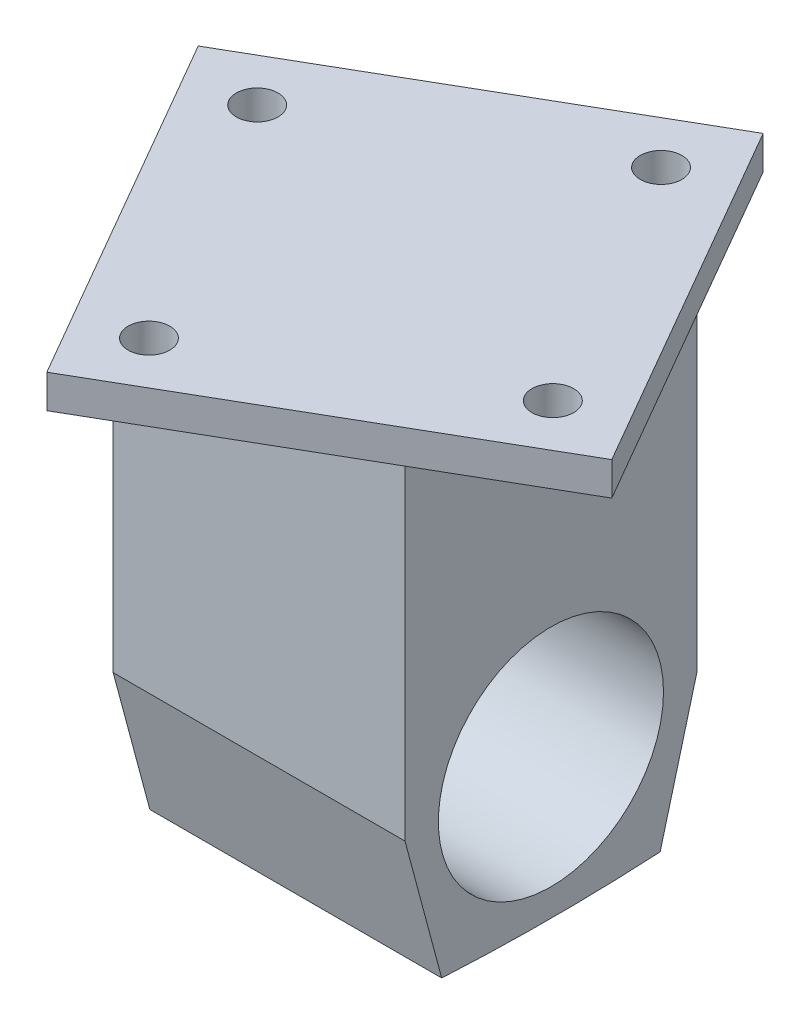
SolidWorks part; units mm, degrees
material "ABS"
ref_plane "Front Plane" through (0, 0, 0) normal (0, 0, 1) x (1, 0, 0)
ref_plane "Top Plane" through (0, 0, 0) normal (0, 1, 0) x (1, 0, 0)
ref_plane "Right Plane" through (0, 0, 0) normal (1, 0, 0) x (0, 0, -1)
sketch "Sketch1" plane through (0, 0, 0) normal (0, 1, 0) x (1, 0, 0)
  line L1 (-22.225, -22.225) -> (22.225, -22.225)
  line L2 (-22.225, -22.225) -> (-22.225, 22.225)
  line L3 (-22.225, 22.225) -> (22.225, 22.225)
  line L4 (22.225, -22.225) -> (22.225, 22.225)
  line L5 (-22.225, -22.225) -> (22.225, 22.225) construction
  line L6 (-22.225, 22.225) -> (22.225, -22.225) construction
  point P0 (0, 0)
extrude "Boss-Extrude1" add sketch "Sketch1" along normal blind 50.292
sketch "Sketch2" plane through (22.225, 0, 0) normal (1, 0, 0) x (0, 0, -1)
  line L0 (-22.225, 0) -> (-16.6371, -20.8543)
  line L1 (22.225, 0) -> (16.6371, -20.8543)
  line L2 (-22.225, 0) -> (22.225, 0)
  line L3 (-22.225, 0) -> (22.225, 0) construction
  arc A1 (16.6371, -20.8543) -> (-16.6371, -20.8543) centre (0, 278.6719) cw
  point P9 (0, 0)
  dimension "D1" = 21.59
  dimension "D2" = 21.59
  dimension "D3" = 75
  dimension "D4" = 75
extrude "Boss-Extrude2" add sketch "Sketch2" against normal up to vertex (44.45 mm away) contours L0 A1 L1 L2 up to point (-22.225, 0, -22.225)
sketch "Sketch3" plane through (22.225, 0, 0) normal (1, 0, 0) x (0, 0, -1)
  circle A0 centre (0, 0) radius 17.145
extrude "Cut-Extrude1" cut sketch "Sketch3" against normal blind 127 contours A0
sketch "Sketch4" plane through (0, 50.292, 0) normal (0, 1, 0) x (1, 0, 0)
  line L0 (-46.8473, 12.5527) -> (46.8473, -12.5527) construction
  line L5 (-13.6389, -50.901) -> (13.6389, 50.901) construction
  line L6 (43.0243, -11.5283) -> (-11.5283, -43.0243)
  line L11 (-11.5283, -43.0243) -> (-43.0243, 11.5283)
  line L12 (-43.0243, 11.5283) -> (11.5283, 43.0243)
  line L13 (11.5283, 43.0243) -> (43.0243, -11.5283)
  line L14 (-11.5283, -43.0243) -> (11.5283, 43.0243) construction
  line L15 (-43.0243, 11.5283) -> (43.0243, -11.5283) construction
  point P1 (0, 0)
  point P4 (0, 0)
  point P11 (0, 0)
  dimension "D1" = 62.992
  dimension "D2" = 62.992
  dimension "D3" = 0
  dimension "D4" = 0
extrude "Boss-Extrude3" add sketch "Sketch4" along normal blind 5.08
sketch "Sketch5" plane through (0, 55.372, 0) normal (0, 1, 0) x (1, 0, 0)
  line L2 (30.7571, -8.2413) -> (43.0243, -11.5283) construction
  line L3 (-8.2413, -30.7571) -> (-11.5283, -43.0243) construction
  line L4 (-30.7571, 8.2413) -> (-43.0243, 11.5283) construction
  line L5 (8.2413, 30.7571) -> (11.5283, 43.0243) construction
  line L6 (11.5283, 43.0243) -> (-43.0243, 11.5283) construction
  line L7 (43.0243, -11.5283) -> (11.5283, 43.0243) construction
  line L8 (-43.0243, 11.5283) -> (-11.5283, -43.0243) construction
  circle A0 centre (30.7571, -8.2413) radius 3.175
  circle A1 centre (-8.2413, -30.7571) radius 3.175
  circle A2 centre (8.2413, 30.7571) radius 3.175
  circle A3 centre (-30.7571, 8.2413) radius 3.175
  dimension "D2" = 6.35
  dimension "D4" = 6.35
  dimension "D11" = 6.35
  dimension "D12" = 6.35
  dimension "D1" = 12.7
  dimension "D3" = 45
  dimension "D5" = 12.7
  dimension "D6" = 45
  dimension "D7" = 12.7
  dimension "D8" = 45
  dimension "D9" = 12.7
  dimension "D10" = 45
extrude "Cut-Extrude2" cut sketch "Sketch5" against normal through all
